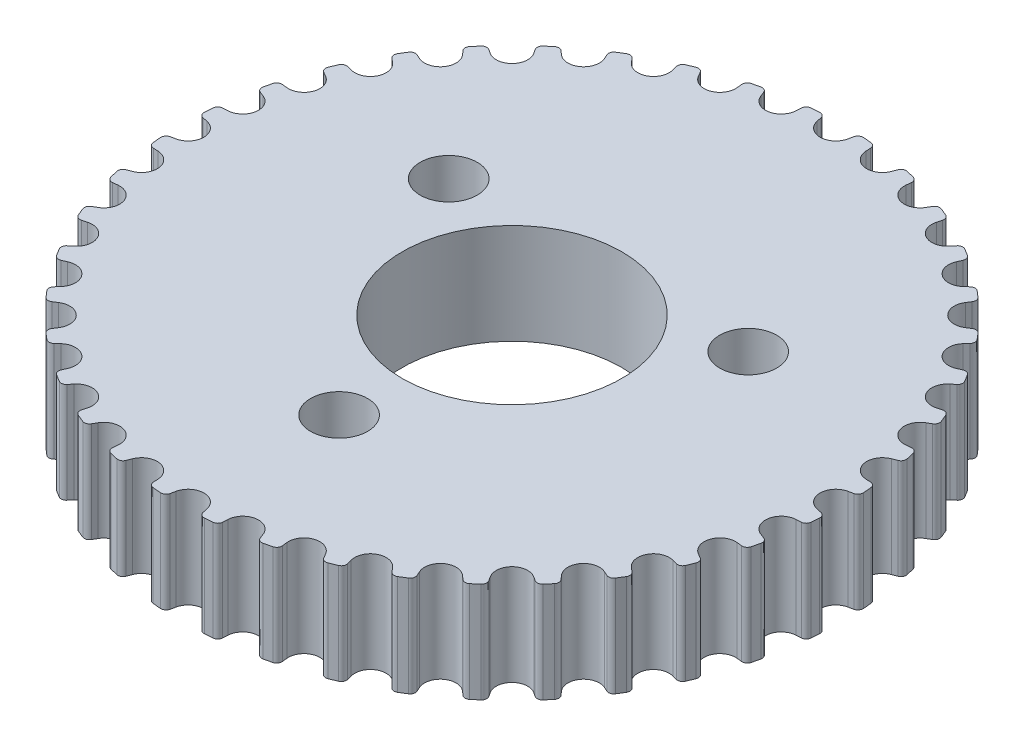
SolidWorks part; units mm, degrees
ref_plane "Front Plane" through (0, 0, 0) normal (0, 0, 1) x (1, 0, 0)
ref_plane "Top Plane" through (0, 0, 0) normal (0, 1, 0) x (1, 0, 0)
ref_plane "Right Plane" through (0, 0, 0) normal (1, 0, 0) x (0, 0, -1)
sketch "Sketch1" plane through (0, 0, 0) normal (0, 1, 0) x (1, 0, 0)
  circle A0 centre (0, 0) radius 19.0986
  dimension "D1" = 38.1972
extrude "Boss-Extrude1" add sketch "Sketch1" along normal blind 5.8
sketch "Sketch2" plane through (0, 5.8, 0) normal (0, 1, 0) x (1, 0, 0)
  line L0 (0, 0) -> (0, 19.0986) construction
  line L1 (-0.89, 18.5387) -> (-0.95, 18.82)
  line L2 (-2.9877, 18.8635) -> (-2.9877, 19.0986)
  line L3 (-2.9877, 19.0986) -> (2.9877, 19.0986)
  line L4 (0.89, 18.5387) -> (0.95, 18.82)
  line L5 (2.9877, 18.8635) -> (2.9877, 19.0986)
  circle A0 centre (0, 0) radius 19.0986 construction
  arc A1 (0.89, 18.5387) -> (-0.89, 18.5387) centre (0, 18.7286) cw
  arc A2 (-0.95, 18.82) -> (-1.2632, 19.0568) centre (-1.2434, 18.7574) ccw
  arc A4 (0.95, 18.82) -> (1.2632, 19.0568) centre (1.2434, 18.7574) cw
  arc A5 (-1.2632, 19.0568) -> (-2.9877, 18.8635) centre (0, 0) ccw
  arc A6 (1.2632, 19.0568) -> (2.9877, 18.8635) centre (0, 0) cw
  circle A8 centre (0, 0) radius 19.0986 construction
  point P11 (0, 19.0986)
  point P19 (0, 17.8186)
  dimension "D3" = 0.3
  dimension "D5" = 0.91
  dimension "D2" = 0.95
  dimension "D4" = 1.28
  dimension "D6" = 9
extrude "Cut-Extrude1" cut sketch "Sketch2" against normal through all
pattern_circular "CirPattern1" count 40 over 360 about axis through (0, 5.8, 0) along (0, -1, 0) of "Cut-Extrude1"
sketch "Sketch3" plane through (0, 0, 0) normal (0, -1, 0) x (1, 0, 0)
  circle A0 centre (0, 0) radius 6.35
  dimension "D1" = 12.7
extrude "Cut-Extrude2" cut sketch "Sketch3" against normal through all
sketch "Sketch4" plane through (0, 0, 0) normal (0, -1, 0) x (1, 0, 0)
  line L0 (0, 0) -> (0, 10) construction
  circle A0 centre (0, 10) radius 1.65
  circle A1 centre (8.6603, -5) radius 1.65
  circle A2 centre (-8.6603, -5) radius 1.65
  point P14 (0, 0)
  dimension "D1" = 3.3
  dimension "D2" = 10
  dimension "D3" = 3
extrude "Cut-Extrude3" cut sketch "Sketch4" against normal through all
sketch "Sketch5" plane through (0, 0, 0) normal (0, -1, 0) x (1, 0, 0)
  line L90 (-18.8409, 0.8522) -> (-18.5596, 0.7922)
  line L91 (-18.8409, 0.8522) -> (-18.5596, 0.7922)
  line L92 (-18.5596, -0.7922) -> (-18.8409, -0.8522)
  line L93 (-18.5596, -0.7922) -> (-18.8409, -0.8522)
  line L94 (-18.7423, -2.1057) -> (-18.455, -2.1209)
  line L95 (-18.7423, -2.1057) -> (-18.455, -2.1209)
  line L96 (-18.2071, -3.6858) -> (-18.4756, -3.7891)
  line L97 (-18.2071, -3.6858) -> (-18.4756, -3.7891)
  line L98 (-18.1821, -5.0117) -> (-17.896, -4.9818)
  line L99 (-18.1821, -5.0117) -> (-17.896, -4.9818)
  line L100 (-17.4064, -6.4886) -> (-17.6554, -6.6327)
  line L101 (-17.4064, -6.4886) -> (-17.6554, -6.6327)
  line L102 (-17.1743, -7.7943) -> (-16.8963, -7.72)
  line L103 (-17.1743, -7.7943) -> (-16.8963, -7.72)
  line L104 (-16.177, -9.1317) -> (-16.4005, -9.3129)
  line L105 (-16.177, -9.1317) -> (-16.4005, -9.3129)
  line L106 (-15.7435, -10.385) -> (-15.4806, -10.2682)
  line L107 (-15.7435, -10.385) -> (-15.4806, -10.2682)
  line L108 (-14.5494, -11.5499) -> (-14.7417, -11.7639)
  line L109 (-14.5494, -11.5499) -> (-14.7417, -11.7639)
  line L110 (-13.9251, -12.7199) -> (-13.6837, -12.5634)
  line L111 (-13.9251, -12.7199) -> (-13.6837, -12.5634)
  line L112 (-12.5634, -13.6837) -> (-12.7199, -13.9251)
  line L113 (-12.5634, -13.6837) -> (-12.7199, -13.9251)
  line L114 (-11.7639, -14.7417) -> (-11.5499, -14.5494)
  line L115 (-11.7639, -14.7417) -> (-11.5499, -14.5494)
  line L116 (-10.2682, -15.4806) -> (-10.385, -15.7435)
  line L117 (-10.2682, -15.4806) -> (-10.385, -15.7435)
  line L118 (-9.3129, -16.4005) -> (-9.1317, -16.177)
  line L119 (-9.3129, -16.4005) -> (-9.1317, -16.177)
  line L120 (6.4886, -17.4064) -> (6.6327, -17.6554)
  line L121 (7.7943, -17.1743) -> (7.72, -16.8963)
  line L122 (9.1317, -16.177) -> (9.3129, -16.4005)
  line L123 (10.385, -15.7435) -> (10.2682, -15.4806)
  line L124 (11.5499, -14.5494) -> (11.7639, -14.7417)
  line L125 (12.7199, -13.9251) -> (12.5634, -13.6837)
  line L126 (13.6837, -12.5634) -> (13.9251, -12.7199)
  line L127 (14.7417, -11.7639) -> (14.5494, -11.5499)
  line L128 (15.4806, -10.2682) -> (15.7435, -10.385)
  line L129 (16.4005, -9.3129) -> (16.177, -9.1317)
  line L130 (16.8963, -7.72) -> (17.1743, -7.7943)
  line L131 (17.6554, -6.6327) -> (17.4064, -6.4886)
  line L132 (17.896, -4.9818) -> (18.1821, -5.0117)
  line L133 (18.4756, -3.7891) -> (18.2071, -3.6858)
  line L134 (18.455, -2.1209) -> (18.7423, -2.1057)
  line L135 (18.8409, -0.8522) -> (18.5596, -0.7922)
  line L136 (18.5596, 0.7922) -> (18.8409, 0.8522)
  line L137 (18.7423, 2.1057) -> (18.455, 2.1209)
  line L138 (18.2071, 3.6858) -> (18.4756, 3.7891)
  line L139 (18.1821, 5.0117) -> (17.896, 4.9818)
  line L140 (17.4064, 6.4886) -> (17.6554, 6.6327)
  line L141 (17.1743, 7.7943) -> (16.8963, 7.72)
  line L142 (16.177, 9.1317) -> (16.4005, 9.3129)
  line L143 (15.7435, 10.385) -> (15.4806, 10.2682)
  line L144 (14.5494, 11.5499) -> (14.7417, 11.7639)
  line L145 (13.9251, 12.7199) -> (13.6837, 12.5634)
  line L146 (12.5634, 13.6837) -> (12.7199, 13.9251)
  line L147 (11.7639, 14.7417) -> (11.5499, 14.5494)
  line L148 (10.2682, 15.4806) -> (10.385, 15.7435)
  line L149 (9.3129, 16.4005) -> (9.1317, 16.177)
  line L150 (7.72, 16.8963) -> (7.7943, 17.1743)
  line L151 (6.6327, 17.6554) -> (6.4886, 17.4064)
  line L152 (4.9818, 17.896) -> (5.0117, 18.1821)
  line L153 (3.7891, 18.4756) -> (3.6858, 18.2071)
  line L154 (2.1209, 18.455) -> (2.1057, 18.7423)
  line L155 (0.8522, 18.8409) -> (0.7922, 18.5596)
  line L156 (-0.7922, 18.5596) -> (-0.8522, 18.8409)
  line L157 (-2.1057, 18.7423) -> (-2.1209, 18.455)
  line L158 (-3.6858, 18.2071) -> (-3.7891, 18.4756)
  line L159 (-5.0117, 18.1821) -> (-4.9818, 17.896)
  line L160 (-6.4886, 17.4064) -> (-6.6327, 17.6554)
  line L161 (-7.7943, 17.1743) -> (-7.72, 16.8963)
  line L162 (-9.1317, 16.177) -> (-9.3129, 16.4005)
  line L163 (-10.385, 15.7435) -> (-10.2682, 15.4806)
  line L164 (-11.5499, 14.5494) -> (-11.7639, 14.7417)
  line L165 (-12.7199, 13.9251) -> (-12.5634, 13.6837)
  line L166 (-13.6837, 12.5634) -> (-13.9251, 12.7199)
  line L167 (-14.7417, 11.7639) -> (-14.5494, 11.5499)
  line L168 (-15.4806, 10.2682) -> (-15.7435, 10.385)
  line L169 (-16.4005, 9.3129) -> (-16.177, 9.1317)
  line L170 (-16.8963, 7.72) -> (-17.1743, 7.7943)
  line L171 (-17.6554, 6.6327) -> (-17.4064, 6.4886)
  line L172 (-17.896, 4.9818) -> (-18.1821, 5.0117)
  line L173 (-18.4756, 3.7891) -> (-18.2071, 3.6858)
  line L174 (-18.455, 2.1209) -> (-18.7423, 2.1057)
  line L175 (-0.8522, -18.8409) -> (-0.7922, -18.5596)
  line L176 (0.7922, -18.5596) -> (0.8522, -18.8409)
  line L177 (2.1057, -18.7423) -> (2.1209, -18.455)
  line L178 (3.6858, -18.2071) -> (3.7891, -18.4756)
  line L179 (5.0117, -18.1821) -> (4.9818, -17.896)
  line L180 (6.4886, -17.4064) -> (6.6327, -17.6554)
  line L181 (7.7943, -17.1743) -> (7.72, -16.8963)
  line L182 (9.1317, -16.177) -> (9.3129, -16.4005)
  line L183 (10.385, -15.7435) -> (10.2682, -15.4806)
  line L184 (11.5499, -14.5494) -> (11.7639, -14.7417)
  line L185 (12.7199, -13.9251) -> (12.5634, -13.6837)
  line L186 (13.6837, -12.5634) -> (13.9251, -12.7199)
  line L187 (14.7417, -11.7639) -> (14.5494, -11.5499)
  line L188 (15.4806, -10.2682) -> (15.7435, -10.385)
  line L189 (16.4005, -9.3129) -> (16.177, -9.1317)
  line L190 (16.8963, -7.72) -> (17.1743, -7.7943)
  line L191 (17.6554, -6.6327) -> (17.4064, -6.4886)
  line L192 (17.896, -4.9818) -> (18.1821, -5.0117)
  line L193 (18.4756, -3.7891) -> (18.2071, -3.6858)
  line L194 (18.455, -2.1209) -> (18.7423, -2.1057)
  line L195 (18.8409, -0.8522) -> (18.5596, -0.7922)
  line L196 (18.5596, 0.7922) -> (18.8409, 0.8522)
  line L197 (18.7423, 2.1057) -> (18.455, 2.1209)
  line L198 (18.2071, 3.6858) -> (18.4756, 3.7891)
  line L199 (18.1821, 5.0117) -> (17.896, 4.9818)
  line L200 (17.4064, 6.4886) -> (17.6554, 6.6327)
  line L201 (17.1743, 7.7943) -> (16.8963, 7.72)
  line L202 (16.177, 9.1317) -> (16.4005, 9.3129)
  line L203 (15.7435, 10.385) -> (15.4806, 10.2682)
  line L204 (14.5494, 11.5499) -> (14.7417, 11.7639)
  line L205 (13.9251, 12.7199) -> (13.6837, 12.5634)
  line L206 (12.5634, 13.6837) -> (12.7199, 13.9251)
  line L207 (11.7639, 14.7417) -> (11.5499, 14.5494)
  line L208 (10.2682, 15.4806) -> (10.385, 15.7435)
  line L209 (9.3129, 16.4005) -> (9.1317, 16.177)
  line L210 (7.72, 16.8963) -> (7.7943, 17.1743)
  line L211 (6.6327, 17.6554) -> (6.4886, 17.4064)
  line L212 (4.9818, 17.896) -> (5.0117, 18.1821)
  line L213 (3.7891, 18.4756) -> (3.6858, 18.2071)
  line L214 (2.1209, 18.455) -> (2.1057, 18.7423)
  line L215 (0.8522, 18.8409) -> (0.7922, 18.5596)
  line L216 (-0.7922, 18.5596) -> (-0.8522, 18.8409)
  line L217 (-2.1057, 18.7423) -> (-2.1209, 18.455)
  line L218 (-3.6858, 18.2071) -> (-3.7891, 18.4756)
  line L219 (-5.0117, 18.1821) -> (-4.9818, 17.896)
  line L220 (-6.4886, 17.4064) -> (-6.6327, 17.6554)
  line L221 (-7.7943, 17.1743) -> (-7.72, 16.8963)
  line L222 (-9.1317, 16.177) -> (-9.3129, 16.4005)
  line L223 (-10.385, 15.7435) -> (-10.2682, 15.4806)
  line L224 (-11.5499, 14.5494) -> (-11.7639, 14.7417)
  line L225 (-12.7199, 13.9251) -> (-12.5634, 13.6837)
  line L226 (-13.6837, 12.5634) -> (-13.9251, 12.7199)
  line L227 (-14.7417, 11.7639) -> (-14.5494, 11.5499)
  line L228 (-15.4806, 10.2682) -> (-15.7435, 10.385)
  line L229 (-16.4005, 9.3129) -> (-16.177, 9.1317)
  line L230 (-16.8963, 7.72) -> (-17.1743, 7.7943)
  line L231 (-17.6554, 6.6327) -> (-17.4064, 6.4886)
  line L232 (-17.896, 4.9818) -> (-18.1821, 5.0117)
  line L233 (-18.4756, 3.7891) -> (-18.2071, 3.6858)
  line L234 (-18.455, 2.1209) -> (-18.7423, 2.1057)
  line L235 (-0.8522, -18.8409) -> (-0.7922, -18.5596)
  line L236 (0.7922, -18.5596) -> (0.8522, -18.8409)
  line L237 (2.1057, -18.7423) -> (2.1209, -18.455)
  line L238 (3.6858, -18.2071) -> (3.7891, -18.4756)
  line L239 (5.0117, -18.1821) -> (4.9818, -17.896)
  line L240 (-7.72, -16.8963) -> (-7.7943, -17.1743)
  line L241 (-7.72, -16.8963) -> (-7.7943, -17.1743)
  line L242 (-6.6327, -17.6554) -> (-6.4886, -17.4064)
  line L243 (-6.6327, -17.6554) -> (-6.4886, -17.4064)
  line L244 (-4.9818, -17.896) -> (-5.0117, -18.1821)
  line L245 (-4.9818, -17.896) -> (-5.0117, -18.1821)
  line L246 (-3.7891, -18.4756) -> (-3.6858, -18.2071)
  line L247 (-3.7891, -18.4756) -> (-3.6858, -18.2071)
  line L248 (-2.1209, -18.455) -> (-2.1057, -18.7423)
  line L249 (-2.1209, -18.455) -> (-2.1057, -18.7423)
  circle A120 centre (0, 0) radius 17.8186
  arc A121 (12.4795, 13.7381) -> (13.7381, 12.4795) centre (13.2431, 13.2431) ccw construction
  arc A182 (-19.1566, 1.2699) -> (-18.8409, 0.8522) centre (-18.7574, 1.2434) ccw
  arc A183 (-19.1566, 1.2699) -> (-18.8409, 0.8522) centre (-18.7574, 1.2434) ccw
  arc A184 (-18.5596, -0.7922) -> (-18.5596, 0.7922) centre (-18.7286, 0) ccw
  arc A185 (-18.5596, -0.7922) -> (-18.5596, 0.7922) centre (-18.7286, 0) ccw
  arc A186 (-18.8409, -0.8522) -> (-19.1566, -1.2699) centre (-18.7574, -1.2434) ccw
  arc A187 (-18.8409, -0.8522) -> (-19.1566, -1.2699) centre (-18.7574, -1.2434) ccw
  arc A188 (-19.1566, -1.2699) -> (-19.1194, -1.7425) centre (0, 0) ccw
  arc A189 (-19.1566, -1.2699) -> (-19.1194, -1.7425) centre (0, 0) ccw
  arc A190 (-19.1194, -1.7425) -> (-18.7423, -2.1057) centre (-18.721, -1.7062) ccw
  arc A191 (-19.1194, -1.7425) -> (-18.7423, -2.1057) centre (-18.721, -1.7062) ccw
  arc A192 (-18.2071, -3.6858) -> (-18.455, -2.1209) centre (-18.498, -2.9298) ccw
  arc A193 (-18.2071, -3.6858) -> (-18.455, -2.1209) centre (-18.498, -2.9298) ccw
  arc A194 (-18.4756, -3.7891) -> (-18.7221, -4.251) centre (-18.332, -4.1624) ccw
  arc A195 (-18.4756, -3.7891) -> (-18.7221, -4.251) centre (-18.332, -4.1624) ccw
  arc A196 (-18.7221, -4.251) -> (-18.6114, -4.712) centre (0, 0) ccw
  arc A197 (-18.7221, -4.251) -> (-18.6114, -4.712) centre (0, 0) ccw
  arc A198 (-18.6114, -4.712) -> (-18.1821, -5.0117) centre (-18.2236, -4.6138) ccw
  arc A199 (-18.6114, -4.712) -> (-18.1821, -5.0117) centre (-18.2236, -4.6138) ccw
  arc A200 (-17.4064, -6.4886) -> (-17.896, -4.9818) centre (-17.812, -5.7875) ccw
  arc A201 (-17.4064, -6.4886) -> (-17.896, -4.9818) centre (-17.812, -5.7875) ccw
  arc A202 (-17.6554, -6.6327) -> (-17.8266, -7.1274) centre (-17.4551, -6.9789) ccw
  arc A203 (-17.6554, -6.6327) -> (-17.8266, -7.1274) centre (-17.4551, -6.9789) ccw
  arc A204 (-17.8266, -7.1274) -> (-17.6451, -7.5654) centre (0, 0) ccw
  arc A205 (-17.8266, -7.1274) -> (-17.6451, -7.5654) centre (0, 0) ccw
  arc A206 (-17.6451, -7.5654) -> (-17.1743, -7.7943) centre (-17.2775, -7.4078) ccw
  arc A207 (-17.6451, -7.5654) -> (-17.1743, -7.7943) centre (-17.2775, -7.4078) ccw
  arc A208 (-16.177, -9.1317) -> (-16.8963, -7.72) centre (-16.6873, -8.5026) ccw
  arc A209 (-16.177, -9.1317) -> (-16.8963, -7.72) centre (-16.6873, -8.5026) ccw
  arc A210 (-16.4005, -9.3129) -> (-16.4921, -9.8283) centre (-16.1485, -9.6236) ccw
  arc A211 (-16.4005, -9.3129) -> (-16.4921, -9.8283) centre (-16.1485, -9.6236) ccw
  arc A212 (-16.4921, -9.8283) -> (-16.2444, -10.2326) centre (0, 0) ccw
  arc A213 (-16.4921, -9.8283) -> (-16.2444, -10.2326) centre (0, 0) ccw
  arc A214 (-16.2444, -10.2326) -> (-15.7435, -10.385) centre (-15.9059, -10.0194) ccw
  arc A215 (-16.2444, -10.2326) -> (-15.7435, -10.385) centre (-15.9059, -10.0194) ccw
  arc A216 (-14.5494, -11.5499) -> (-15.4806, -10.2682) centre (-15.1518, -11.0084) ccw
  arc A217 (-14.5494, -11.5499) -> (-15.4806, -10.2682) centre (-15.1518, -11.0084) ccw
  arc A218 (-14.7417, -11.7639) -> (-14.7516, -12.2873) centre (-14.4442, -12.0313) ccw
  arc A219 (-14.7417, -11.7639) -> (-14.7516, -12.2873) centre (-14.4442, -12.0313) ccw
  arc A220 (-14.7516, -12.2873) -> (-14.4436, -12.6478) centre (0, 0) ccw
  arc A221 (-14.7516, -12.2873) -> (-14.4436, -12.6478) centre (0, 0) ccw
  arc A222 (-14.4436, -12.6478) -> (-13.9251, -12.7199) centre (-14.1427, -12.3843) ccw
  arc A223 (-14.4436, -12.6478) -> (-13.9251, -12.7199) centre (-14.1427, -12.3843) ccw
  arc A224 (-12.5634, -13.6837) -> (-13.6837, -12.5634) centre (-13.2431, -13.2431) ccw
  arc A225 (-12.5634, -13.6837) -> (-13.6837, -12.5634) centre (-13.2431, -13.2431) ccw
  arc A226 (-12.7199, -13.9251) -> (-12.6478, -14.4436) centre (-12.3843, -14.1427) ccw
  arc A227 (-12.7199, -13.9251) -> (-12.6478, -14.4436) centre (-12.3843, -14.1427) ccw
  arc A228 (-12.6478, -14.4436) -> (-12.2873, -14.7516) centre (0, 0) ccw
  arc A229 (-12.6478, -14.4436) -> (-12.2873, -14.7516) centre (0, 0) ccw
  arc A230 (-12.2873, -14.7516) -> (-11.7639, -14.7417) centre (-12.0313, -14.4442) ccw
  arc A231 (-12.2873, -14.7516) -> (-11.7639, -14.7417) centre (-12.0313, -14.4442) ccw
  arc A232 (-10.2682, -15.4806) -> (-11.5499, -14.5494) centre (-11.0084, -15.1518) ccw
  arc A233 (-10.2682, -15.4806) -> (-11.5499, -14.5494) centre (-11.0084, -15.1518) ccw
  arc A234 (-10.385, -15.7435) -> (-10.2326, -16.2444) centre (-10.0194, -15.9059) ccw
  arc A235 (-10.385, -15.7435) -> (-10.2326, -16.2444) centre (-10.0194, -15.9059) ccw
  arc A236 (-10.2326, -16.2444) -> (-9.8283, -16.4921) centre (0, 0) ccw
  arc A237 (-10.2326, -16.2444) -> (-9.8283, -16.4921) centre (0, 0) ccw
  arc A238 (-9.8283, -16.4921) -> (-9.3129, -16.4005) centre (-9.6236, -16.1485) ccw
  arc A239 (-9.8283, -16.4921) -> (-9.3129, -16.4005) centre (-9.6236, -16.1485) ccw
  arc A240 (6.6327, -17.6554) -> (7.1274, -17.8266) centre (6.9789, -17.4551) ccw
  arc A241 (7.1274, -17.8266) -> (7.5654, -17.6451) centre (0, 0) ccw
  arc A242 (7.5654, -17.6451) -> (7.7943, -17.1743) centre (7.4078, -17.2775) ccw
  arc A243 (9.1317, -16.177) -> (7.72, -16.8963) centre (8.5026, -16.6873) ccw
  arc A244 (9.3129, -16.4005) -> (9.8283, -16.4921) centre (9.6236, -16.1485) ccw
  arc A245 (9.8283, -16.4921) -> (10.2326, -16.2444) centre (0, 0) ccw
  arc A246 (10.2326, -16.2444) -> (10.385, -15.7435) centre (10.0194, -15.9059) ccw
  arc A247 (11.5499, -14.5494) -> (10.2682, -15.4806) centre (11.0084, -15.1518) ccw
  arc A248 (11.7639, -14.7417) -> (12.2873, -14.7516) centre (12.0313, -14.4442) ccw
  arc A249 (12.2873, -14.7516) -> (12.6478, -14.4436) centre (0, 0) ccw
  arc A250 (12.6478, -14.4436) -> (12.7199, -13.9251) centre (12.3843, -14.1427) ccw
  arc A251 (13.6837, -12.5634) -> (12.5634, -13.6837) centre (13.2431, -13.2431) ccw
  arc A252 (13.9251, -12.7199) -> (14.4436, -12.6478) centre (14.1427, -12.3843) ccw
  arc A253 (14.4436, -12.6478) -> (14.7516, -12.2873) centre (0, 0) ccw
  arc A254 (14.7516, -12.2873) -> (14.7417, -11.7639) centre (14.4442, -12.0313) ccw
  arc A255 (15.4806, -10.2682) -> (14.5494, -11.5499) centre (15.1518, -11.0084) ccw
  arc A256 (15.7435, -10.385) -> (16.2444, -10.2326) centre (15.9059, -10.0194) ccw
  arc A257 (16.2444, -10.2326) -> (16.4921, -9.8283) centre (0, 0) ccw
  arc A258 (16.4921, -9.8283) -> (16.4005, -9.3129) centre (16.1485, -9.6236) ccw
  arc A259 (16.8963, -7.72) -> (16.177, -9.1317) centre (16.6873, -8.5026) ccw
  arc A260 (17.1743, -7.7943) -> (17.6451, -7.5654) centre (17.2775, -7.4078) ccw
  arc A261 (17.6451, -7.5654) -> (17.8266, -7.1274) centre (0, 0) ccw
  arc A262 (17.8266, -7.1274) -> (17.6554, -6.6327) centre (17.4551, -6.9789) ccw
  arc A263 (17.896, -4.9818) -> (17.4064, -6.4886) centre (17.812, -5.7875) ccw
  arc A264 (18.1821, -5.0117) -> (18.6114, -4.712) centre (18.2236, -4.6138) ccw
  arc A265 (18.6114, -4.712) -> (18.7221, -4.251) centre (0, 0) ccw
  arc A266 (18.7221, -4.251) -> (18.4756, -3.7891) centre (18.332, -4.1624) ccw
  arc A267 (18.455, -2.1209) -> (18.2071, -3.6858) centre (18.498, -2.9298) ccw
  arc A268 (18.7423, -2.1057) -> (19.1194, -1.7425) centre (18.721, -1.7062) ccw
  arc A269 (19.1194, -1.7425) -> (19.1566, -1.2699) centre (0, 0) ccw
  arc A270 (19.1566, -1.2699) -> (18.8409, -0.8522) centre (18.7574, -1.2434) ccw
  arc A271 (18.5596, 0.7922) -> (18.5596, -0.7922) centre (18.7286, 0) ccw
  arc A272 (18.8409, 0.8522) -> (19.1566, 1.2699) centre (18.7574, 1.2434) ccw
  arc A273 (19.1566, 1.2699) -> (19.1194, 1.7425) centre (0, 0) ccw
  arc A274 (19.1194, 1.7425) -> (18.7423, 2.1057) centre (18.721, 1.7062) ccw
  arc A275 (18.2071, 3.6858) -> (18.455, 2.1209) centre (18.498, 2.9298) ccw
  arc A276 (18.4756, 3.7891) -> (18.7221, 4.251) centre (18.332, 4.1624) ccw
  arc A277 (18.7221, 4.251) -> (18.6114, 4.712) centre (0, 0) ccw
  arc A278 (18.6114, 4.712) -> (18.1821, 5.0117) centre (18.2236, 4.6138) ccw
  arc A279 (17.4064, 6.4886) -> (17.896, 4.9818) centre (17.812, 5.7875) ccw
  arc A280 (17.6554, 6.6327) -> (17.8266, 7.1274) centre (17.4551, 6.9789) ccw
  arc A281 (17.8266, 7.1274) -> (17.6451, 7.5654) centre (0, 0) ccw
  arc A282 (17.6451, 7.5654) -> (17.1743, 7.7943) centre (17.2775, 7.4078) ccw
  arc A283 (16.177, 9.1317) -> (16.8963, 7.72) centre (16.6873, 8.5026) ccw
  arc A284 (16.4005, 9.3129) -> (16.4921, 9.8283) centre (16.1485, 9.6236) ccw
  arc A285 (16.4921, 9.8283) -> (16.2444, 10.2326) centre (0, 0) ccw
  arc A286 (16.2444, 10.2326) -> (15.7435, 10.385) centre (15.9059, 10.0194) ccw
  arc A287 (14.5494, 11.5499) -> (15.4806, 10.2682) centre (15.1518, 11.0084) ccw
  arc A288 (14.7417, 11.7639) -> (14.7516, 12.2873) centre (14.4442, 12.0313) ccw
  arc A289 (14.7516, 12.2873) -> (14.4436, 12.6478) centre (0, 0) ccw
  arc A290 (14.4436, 12.6478) -> (13.9251, 12.7199) centre (14.1427, 12.3843) ccw
  arc A291 (12.5634, 13.6837) -> (13.6837, 12.5634) centre (13.2431, 13.2431) ccw
  arc A292 (12.7199, 13.9251) -> (12.6478, 14.4436) centre (12.3843, 14.1427) ccw
  arc A293 (12.6478, 14.4436) -> (12.2873, 14.7516) centre (0, 0) ccw
  arc A294 (12.2873, 14.7516) -> (11.7639, 14.7417) centre (12.0313, 14.4442) ccw
  arc A295 (10.2682, 15.4806) -> (11.5499, 14.5494) centre (11.0084, 15.1518) ccw
  arc A296 (10.385, 15.7435) -> (10.2326, 16.2444) centre (10.0194, 15.9059) ccw
  arc A297 (10.2326, 16.2444) -> (9.8283, 16.4921) centre (0, 0) ccw
  arc A298 (9.8283, 16.4921) -> (9.3129, 16.4005) centre (9.6236, 16.1485) ccw
  arc A299 (7.72, 16.8963) -> (9.1317, 16.177) centre (8.5026, 16.6873) ccw
  arc A300 (7.7943, 17.1743) -> (7.5654, 17.6451) centre (7.4078, 17.2775) ccw
  arc A301 (7.5654, 17.6451) -> (7.1274, 17.8266) centre (0, 0) ccw
  arc A302 (7.1274, 17.8266) -> (6.6327, 17.6554) centre (6.9789, 17.4551) ccw
  arc A303 (4.9818, 17.896) -> (6.4886, 17.4064) centre (5.7875, 17.812) ccw
  arc A304 (5.0117, 18.1821) -> (4.712, 18.6114) centre (4.6138, 18.2236) ccw
  arc A305 (4.712, 18.6114) -> (4.251, 18.7221) centre (0, 0) ccw
  arc A306 (4.251, 18.7221) -> (3.7891, 18.4756) centre (4.1624, 18.332) ccw
  arc A307 (2.1209, 18.455) -> (3.6858, 18.2071) centre (2.9298, 18.498) ccw
  arc A308 (2.1057, 18.7423) -> (1.7425, 19.1194) centre (1.7062, 18.721) ccw
  arc A309 (1.7425, 19.1194) -> (1.2699, 19.1566) centre (0, 0) ccw
  arc A310 (1.2699, 19.1566) -> (0.8522, 18.8409) centre (1.2434, 18.7574) ccw
  arc A311 (-0.7922, 18.5596) -> (0.7922, 18.5596) centre (0, 18.7286) ccw
  arc A312 (-0.8522, 18.8409) -> (-1.2699, 19.1566) centre (-1.2434, 18.7574) ccw
  arc A313 (-1.2699, 19.1566) -> (-1.7425, 19.1194) centre (0, 0) ccw
  arc A314 (-1.7425, 19.1194) -> (-2.1057, 18.7423) centre (-1.7062, 18.721) ccw
  arc A315 (-3.6858, 18.2071) -> (-2.1209, 18.455) centre (-2.9298, 18.498) ccw
  arc A316 (-3.7891, 18.4756) -> (-4.251, 18.7221) centre (-4.1624, 18.332) ccw
  arc A317 (-4.251, 18.7221) -> (-4.712, 18.6114) centre (0, 0) ccw
  arc A318 (-4.712, 18.6114) -> (-5.0117, 18.1821) centre (-4.6138, 18.2236) ccw
  arc A319 (-6.4886, 17.4064) -> (-4.9818, 17.896) centre (-5.7875, 17.812) ccw
  arc A320 (-6.6327, 17.6554) -> (-7.1274, 17.8266) centre (-6.9789, 17.4551) ccw
  arc A321 (-7.1274, 17.8266) -> (-7.5654, 17.6451) centre (0, 0) ccw
  arc A322 (-7.5654, 17.6451) -> (-7.7943, 17.1743) centre (-7.4078, 17.2775) ccw
  arc A323 (-9.1317, 16.177) -> (-7.72, 16.8963) centre (-8.5026, 16.6873) ccw
  arc A324 (-9.3129, 16.4005) -> (-9.8283, 16.4921) centre (-9.6236, 16.1485) ccw
  arc A325 (-9.8283, 16.4921) -> (-10.2326, 16.2444) centre (0, 0) ccw
  arc A326 (-10.2326, 16.2444) -> (-10.385, 15.7435) centre (-10.0194, 15.9059) ccw
  arc A327 (-11.5499, 14.5494) -> (-10.2682, 15.4806) centre (-11.0084, 15.1518) ccw
  arc A328 (-11.7639, 14.7417) -> (-12.2873, 14.7516) centre (-12.0313, 14.4442) ccw
  arc A329 (-12.2873, 14.7516) -> (-12.6478, 14.4436) centre (0, 0) ccw
  arc A330 (-12.6478, 14.4436) -> (-12.7199, 13.9251) centre (-12.3843, 14.1427) ccw
  arc A331 (-13.6837, 12.5634) -> (-12.5634, 13.6837) centre (-13.2431, 13.2431) ccw
  arc A332 (-13.9251, 12.7199) -> (-14.4436, 12.6478) centre (-14.1427, 12.3843) ccw
  arc A333 (-14.4436, 12.6478) -> (-14.7516, 12.2873) centre (0, 0) ccw
  arc A334 (-14.7516, 12.2873) -> (-14.7417, 11.7639) centre (-14.4442, 12.0313) ccw
  arc A335 (-15.4806, 10.2682) -> (-14.5494, 11.5499) centre (-15.1518, 11.0084) ccw
  arc A336 (-15.7435, 10.385) -> (-16.2444, 10.2326) centre (-15.9059, 10.0194) ccw
  arc A337 (-16.2444, 10.2326) -> (-16.4921, 9.8283) centre (0, 0) ccw
  arc A338 (-16.4921, 9.8283) -> (-16.4005, 9.3129) centre (-16.1485, 9.6236) ccw
  arc A339 (-16.8963, 7.72) -> (-16.177, 9.1317) centre (-16.6873, 8.5026) ccw
  arc A340 (-17.1743, 7.7943) -> (-17.6451, 7.5654) centre (-17.2775, 7.4078) ccw
  arc A341 (-17.6451, 7.5654) -> (-17.8266, 7.1274) centre (0, 0) ccw
  arc A342 (-17.8266, 7.1274) -> (-17.6554, 6.6327) centre (-17.4551, 6.9789) ccw
  arc A343 (-17.896, 4.9818) -> (-17.4064, 6.4886) centre (-17.812, 5.7875) ccw
  arc A344 (-18.1821, 5.0117) -> (-18.6114, 4.712) centre (-18.2236, 4.6138) ccw
  arc A345 (-18.6114, 4.712) -> (-18.7221, 4.251) centre (0, 0) ccw
  arc A346 (-18.7221, 4.251) -> (-18.4756, 3.7891) centre (-18.332, 4.1624) ccw
  arc A347 (-18.455, 2.1209) -> (-18.2071, 3.6858) centre (-18.498, 2.9298) ccw
  arc A348 (-18.7423, 2.1057) -> (-19.1194, 1.7425) centre (-18.721, 1.7062) ccw
  arc A349 (-19.1194, 1.7425) -> (-19.1566, 1.2699) centre (0, 0) ccw
  arc A350 (-1.2699, -19.1566) -> (-0.8522, -18.8409) centre (-1.2434, -18.7574) ccw
  arc A351 (0.7922, -18.5596) -> (-0.7922, -18.5596) centre (0, -18.7286) ccw
  arc A352 (0.8522, -18.8409) -> (1.2699, -19.1566) centre (1.2434, -18.7574) ccw
  arc A353 (1.2699, -19.1566) -> (1.7425, -19.1194) centre (0, 0) ccw
  arc A354 (1.7425, -19.1194) -> (2.1057, -18.7423) centre (1.7062, -18.721) ccw
  arc A355 (3.6858, -18.2071) -> (2.1209, -18.455) centre (2.9298, -18.498) ccw
  arc A356 (3.7891, -18.4756) -> (4.251, -18.7221) centre (4.1624, -18.332) ccw
  arc A357 (4.251, -18.7221) -> (4.712, -18.6114) centre (0, 0) ccw
  arc A358 (4.712, -18.6114) -> (5.0117, -18.1821) centre (4.6138, -18.2236) ccw
  arc A359 (6.4886, -17.4064) -> (4.9818, -17.896) centre (5.7875, -17.812) ccw
  arc A360 (6.6327, -17.6554) -> (7.1274, -17.8266) centre (6.9789, -17.4551) ccw
  arc A361 (7.1274, -17.8266) -> (7.5654, -17.6451) centre (0, 0) ccw
  arc A362 (7.5654, -17.6451) -> (7.7943, -17.1743) centre (7.4078, -17.2775) ccw
  arc A363 (9.1317, -16.177) -> (7.72, -16.8963) centre (8.5026, -16.6873) ccw
  arc A364 (9.3129, -16.4005) -> (9.8283, -16.4921) centre (9.6236, -16.1485) ccw
  arc A365 (9.8283, -16.4921) -> (10.2326, -16.2444) centre (0, 0) ccw
  arc A366 (10.2326, -16.2444) -> (10.385, -15.7435) centre (10.0194, -15.9059) ccw
  arc A367 (11.5499, -14.5494) -> (10.2682, -15.4806) centre (11.0084, -15.1518) ccw
  arc A368 (11.7639, -14.7417) -> (12.2873, -14.7516) centre (12.0313, -14.4442) ccw
  arc A369 (12.2873, -14.7516) -> (12.6478, -14.4436) centre (0, 0) ccw
  arc A370 (12.6478, -14.4436) -> (12.7199, -13.9251) centre (12.3843, -14.1427) ccw
  arc A371 (13.6837, -12.5634) -> (12.5634, -13.6837) centre (13.2431, -13.2431) ccw
  arc A372 (13.9251, -12.7199) -> (14.4436, -12.6478) centre (14.1427, -12.3843) ccw
  arc A373 (14.4436, -12.6478) -> (14.7516, -12.2873) centre (0, 0) ccw
  arc A374 (14.7516, -12.2873) -> (14.7417, -11.7639) centre (14.4442, -12.0313) ccw
  arc A375 (15.4806, -10.2682) -> (14.5494, -11.5499) centre (15.1518, -11.0084) ccw
  arc A376 (15.7435, -10.385) -> (16.2444, -10.2326) centre (15.9059, -10.0194) ccw
  arc A377 (16.2444, -10.2326) -> (16.4921, -9.8283) centre (0, 0) ccw
  arc A378 (16.4921, -9.8283) -> (16.4005, -9.3129) centre (16.1485, -9.6236) ccw
  arc A379 (16.8963, -7.72) -> (16.177, -9.1317) centre (16.6873, -8.5026) ccw
  arc A380 (17.1743, -7.7943) -> (17.6451, -7.5654) centre (17.2775, -7.4078) ccw
  arc A381 (17.6451, -7.5654) -> (17.8266, -7.1274) centre (0, 0) ccw
  arc A382 (17.8266, -7.1274) -> (17.6554, -6.6327) centre (17.4551, -6.9789) ccw
  arc A383 (17.896, -4.9818) -> (17.4064, -6.4886) centre (17.812, -5.7875) ccw
  arc A384 (18.1821, -5.0117) -> (18.6114, -4.712) centre (18.2236, -4.6138) ccw
  arc A385 (18.6114, -4.712) -> (18.7221, -4.251) centre (0, 0) ccw
  arc A386 (18.7221, -4.251) -> (18.4756, -3.7891) centre (18.332, -4.1624) ccw
  arc A387 (18.455, -2.1209) -> (18.2071, -3.6858) centre (18.498, -2.9298) ccw
  arc A388 (18.7423, -2.1057) -> (19.1194, -1.7425) centre (18.721, -1.7062) ccw
  arc A389 (19.1194, -1.7425) -> (19.1566, -1.2699) centre (0, 0) ccw
  arc A390 (19.1566, -1.2699) -> (18.8409, -0.8522) centre (18.7574, -1.2434) ccw
  arc A391 (18.5596, 0.7922) -> (18.5596, -0.7922) centre (18.7286, 0) ccw
  arc A392 (18.8409, 0.8522) -> (19.1566, 1.2699) centre (18.7574, 1.2434) ccw
  arc A393 (19.1566, 1.2699) -> (19.1194, 1.7425) centre (0, 0) ccw
  arc A394 (19.1194, 1.7425) -> (18.7423, 2.1057) centre (18.721, 1.7062) ccw
  arc A395 (18.2071, 3.6858) -> (18.455, 2.1209) centre (18.498, 2.9298) ccw
  arc A396 (18.4756, 3.7891) -> (18.7221, 4.251) centre (18.332, 4.1624) ccw
  arc A397 (18.7221, 4.251) -> (18.6114, 4.712) centre (0, 0) ccw
  arc A398 (18.6114, 4.712) -> (18.1821, 5.0117) centre (18.2236, 4.6138) ccw
  arc A399 (17.4064, 6.4886) -> (17.896, 4.9818) centre (17.812, 5.7875) ccw
  arc A400 (17.6554, 6.6327) -> (17.8266, 7.1274) centre (17.4551, 6.9789) ccw
  arc A401 (17.8266, 7.1274) -> (17.6451, 7.5654) centre (0, 0) ccw
  arc A402 (17.6451, 7.5654) -> (17.1743, 7.7943) centre (17.2775, 7.4078) ccw
  arc A403 (16.177, 9.1317) -> (16.8963, 7.72) centre (16.6873, 8.5026) ccw
  arc A404 (16.4005, 9.3129) -> (16.4921, 9.8283) centre (16.1485, 9.6236) ccw
  arc A405 (16.4921, 9.8283) -> (16.2444, 10.2326) centre (0, 0) ccw
  arc A406 (16.2444, 10.2326) -> (15.7435, 10.385) centre (15.9059, 10.0194) ccw
  arc A407 (14.5494, 11.5499) -> (15.4806, 10.2682) centre (15.1518, 11.0084) ccw
  arc A408 (14.7417, 11.7639) -> (14.7516, 12.2873) centre (14.4442, 12.0313) ccw
  arc A409 (14.7516, 12.2873) -> (14.4436, 12.6478) centre (0, 0) ccw
  arc A410 (14.4436, 12.6478) -> (13.9251, 12.7199) centre (14.1427, 12.3843) ccw
  arc A411 (12.5634, 13.6837) -> (13.6837, 12.5634) centre (13.2431, 13.2431) ccw
  arc A412 (12.7199, 13.9251) -> (12.6478, 14.4436) centre (12.3843, 14.1427) ccw
  arc A413 (12.6478, 14.4436) -> (12.2873, 14.7516) centre (0, 0) ccw
  arc A414 (12.2873, 14.7516) -> (11.7639, 14.7417) centre (12.0313, 14.4442) ccw
  arc A415 (10.2682, 15.4806) -> (11.5499, 14.5494) centre (11.0084, 15.1518) ccw
  arc A416 (10.385, 15.7435) -> (10.2326, 16.2444) centre (10.0194, 15.9059) ccw
  arc A417 (10.2326, 16.2444) -> (9.8283, 16.4921) centre (0, 0) ccw
  arc A418 (9.8283, 16.4921) -> (9.3129, 16.4005) centre (9.6236, 16.1485) ccw
  arc A419 (7.72, 16.8963) -> (9.1317, 16.177) centre (8.5026, 16.6873) ccw
  arc A420 (7.7943, 17.1743) -> (7.5654, 17.6451) centre (7.4078, 17.2775) ccw
  arc A421 (7.5654, 17.6451) -> (7.1274, 17.8266) centre (0, 0) ccw
  arc A422 (7.1274, 17.8266) -> (6.6327, 17.6554) centre (6.9789, 17.4551) ccw
  arc A423 (4.9818, 17.896) -> (6.4886, 17.4064) centre (5.7875, 17.812) ccw
  arc A424 (5.0117, 18.1821) -> (4.712, 18.6114) centre (4.6138, 18.2236) ccw
  arc A425 (4.712, 18.6114) -> (4.251, 18.7221) centre (0, 0) ccw
  arc A426 (4.251, 18.7221) -> (3.7891, 18.4756) centre (4.1624, 18.332) ccw
  arc A427 (2.1209, 18.455) -> (3.6858, 18.2071) centre (2.9298, 18.498) ccw
  arc A428 (2.1057, 18.7423) -> (1.7425, 19.1194) centre (1.7062, 18.721) ccw
  arc A429 (1.7425, 19.1194) -> (1.2699, 19.1566) centre (0, 0) ccw
  arc A430 (1.2699, 19.1566) -> (0.8522, 18.8409) centre (1.2434, 18.7574) ccw
  arc A431 (-0.7922, 18.5596) -> (0.7922, 18.5596) centre (0, 18.7286) ccw
  arc A432 (-0.8522, 18.8409) -> (-1.2699, 19.1566) centre (-1.2434, 18.7574) ccw
  arc A433 (-1.2699, 19.1566) -> (-1.7425, 19.1194) centre (0, 0) ccw
  arc A434 (-1.7425, 19.1194) -> (-2.1057, 18.7423) centre (-1.7062, 18.721) ccw
  arc A435 (-3.6858, 18.2071) -> (-2.1209, 18.455) centre (-2.9298, 18.498) ccw
  arc A436 (-3.7891, 18.4756) -> (-4.251, 18.7221) centre (-4.1624, 18.332) ccw
  arc A437 (-4.251, 18.7221) -> (-4.712, 18.6114) centre (0, 0) ccw
  arc A438 (-4.712, 18.6114) -> (-5.0117, 18.1821) centre (-4.6138, 18.2236) ccw
  arc A439 (-6.4886, 17.4064) -> (-4.9818, 17.896) centre (-5.7875, 17.812) ccw
  arc A440 (-6.6327, 17.6554) -> (-7.1274, 17.8266) centre (-6.9789, 17.4551) ccw
  arc A441 (-7.1274, 17.8266) -> (-7.5654, 17.6451) centre (0, 0) ccw
  arc A442 (-7.5654, 17.6451) -> (-7.7943, 17.1743) centre (-7.4078, 17.2775) ccw
  arc A443 (-9.1317, 16.177) -> (-7.72, 16.8963) centre (-8.5026, 16.6873) ccw
  arc A444 (-9.3129, 16.4005) -> (-9.8283, 16.4921) centre (-9.6236, 16.1485) ccw
  arc A445 (-9.8283, 16.4921) -> (-10.2326, 16.2444) centre (0, 0) ccw
  arc A446 (-10.2326, 16.2444) -> (-10.385, 15.7435) centre (-10.0194, 15.9059) ccw
  arc A447 (-11.5499, 14.5494) -> (-10.2682, 15.4806) centre (-11.0084, 15.1518) ccw
  arc A448 (-11.7639, 14.7417) -> (-12.2873, 14.7516) centre (-12.0313, 14.4442) ccw
  arc A449 (-12.2873, 14.7516) -> (-12.6478, 14.4436) centre (0, 0) ccw
  arc A450 (-12.6478, 14.4436) -> (-12.7199, 13.9251) centre (-12.3843, 14.1427) ccw
  arc A451 (-13.6837, 12.5634) -> (-12.5634, 13.6837) centre (-13.2431, 13.2431) ccw
  arc A452 (-13.9251, 12.7199) -> (-14.4436, 12.6478) centre (-14.1427, 12.3843) ccw
  arc A453 (-14.4436, 12.6478) -> (-14.7516, 12.2873) centre (0, 0) ccw
  arc A454 (-14.7516, 12.2873) -> (-14.7417, 11.7639) centre (-14.4442, 12.0313) ccw
  arc A455 (-15.4806, 10.2682) -> (-14.5494, 11.5499) centre (-15.1518, 11.0084) ccw
  arc A456 (-15.7435, 10.385) -> (-16.2444, 10.2326) centre (-15.9059, 10.0194) ccw
  arc A457 (-16.2444, 10.2326) -> (-16.4921, 9.8283) centre (0, 0) ccw
  arc A458 (-16.4921, 9.8283) -> (-16.4005, 9.3129) centre (-16.1485, 9.6236) ccw
  arc A459 (-16.8963, 7.72) -> (-16.177, 9.1317) centre (-16.6873, 8.5026) ccw
  arc A460 (-17.1743, 7.7943) -> (-17.6451, 7.5654) centre (-17.2775, 7.4078) ccw
  arc A461 (-17.6451, 7.5654) -> (-17.8266, 7.1274) centre (0, 0) ccw
  arc A462 (-17.8266, 7.1274) -> (-17.6554, 6.6327) centre (-17.4551, 6.9789) ccw
  arc A463 (-17.896, 4.9818) -> (-17.4064, 6.4886) centre (-17.812, 5.7875) ccw
  arc A464 (-18.1821, 5.0117) -> (-18.6114, 4.712) centre (-18.2236, 4.6138) ccw
  arc A465 (-18.6114, 4.712) -> (-18.7221, 4.251) centre (0, 0) ccw
  arc A466 (-18.7221, 4.251) -> (-18.4756, 3.7891) centre (-18.332, 4.1624) ccw
  arc A467 (-18.455, 2.1209) -> (-18.2071, 3.6858) centre (-18.498, 2.9298) ccw
  arc A468 (-18.7423, 2.1057) -> (-19.1194, 1.7425) centre (-18.721, 1.7062) ccw
  arc A469 (-19.1194, 1.7425) -> (-19.1566, 1.2699) centre (0, 0) ccw
  arc A470 (-1.2699, -19.1566) -> (-0.8522, -18.8409) centre (-1.2434, -18.7574) ccw
  arc A471 (0.7922, -18.5596) -> (-0.7922, -18.5596) centre (0, -18.7286) ccw
  arc A472 (0.8522, -18.8409) -> (1.2699, -19.1566) centre (1.2434, -18.7574) ccw
  arc A473 (1.2699, -19.1566) -> (1.7425, -19.1194) centre (0, 0) ccw
  arc A474 (1.7425, -19.1194) -> (2.1057, -18.7423) centre (1.7062, -18.721) ccw
  arc A475 (3.6858, -18.2071) -> (2.1209, -18.455) centre (2.9298, -18.498) ccw
  arc A476 (3.7891, -18.4756) -> (4.251, -18.7221) centre (4.1624, -18.332) ccw
  arc A477 (4.251, -18.7221) -> (4.712, -18.6114) centre (0, 0) ccw
  arc A478 (4.712, -18.6114) -> (5.0117, -18.1821) centre (4.6138, -18.2236) ccw
  arc A479 (6.4886, -17.4064) -> (4.9818, -17.896) centre (5.7875, -17.812) ccw
  arc A480 (-7.72, -16.8963) -> (-9.1317, -16.177) centre (-8.5026, -16.6873) ccw
  arc A481 (-7.72, -16.8963) -> (-9.1317, -16.177) centre (-8.5026, -16.6873) ccw
  arc A482 (-7.7943, -17.1743) -> (-7.5654, -17.6451) centre (-7.4078, -17.2775) ccw
  arc A483 (-7.7943, -17.1743) -> (-7.5654, -17.6451) centre (-7.4078, -17.2775) ccw
  arc A484 (-7.5654, -17.6451) -> (-7.1274, -17.8266) centre (0, 0) ccw
  arc A485 (-7.5654, -17.6451) -> (-7.1274, -17.8266) centre (0, 0) ccw
  arc A486 (-7.1274, -17.8266) -> (-6.6327, -17.6554) centre (-6.9789, -17.4551) ccw
  arc A487 (-7.1274, -17.8266) -> (-6.6327, -17.6554) centre (-6.9789, -17.4551) ccw
  arc A488 (-4.9818, -17.896) -> (-6.4886, -17.4064) centre (-5.7875, -17.812) ccw
  arc A489 (-4.9818, -17.896) -> (-6.4886, -17.4064) centre (-5.7875, -17.812) ccw
  arc A490 (-5.0117, -18.1821) -> (-4.712, -18.6114) centre (-4.6138, -18.2236) ccw
  arc A491 (-5.0117, -18.1821) -> (-4.712, -18.6114) centre (-4.6138, -18.2236) ccw
  arc A492 (-4.712, -18.6114) -> (-4.251, -18.7221) centre (0, 0) ccw
  arc A493 (-4.712, -18.6114) -> (-4.251, -18.7221) centre (0, 0) ccw
  arc A494 (-4.251, -18.7221) -> (-3.7891, -18.4756) centre (-4.1624, -18.332) ccw
  arc A495 (-4.251, -18.7221) -> (-3.7891, -18.4756) centre (-4.1624, -18.332) ccw
  arc A496 (-2.1209, -18.455) -> (-3.6858, -18.2071) centre (-2.9298, -18.498) ccw
  arc A497 (-2.1209, -18.455) -> (-3.6858, -18.2071) centre (-2.9298, -18.498) ccw
  arc A498 (-2.1057, -18.7423) -> (-1.7425, -19.1194) centre (-1.7062, -18.721) ccw
  arc A499 (-2.1057, -18.7423) -> (-1.7425, -19.1194) centre (-1.7062, -18.721) ccw
  arc A500 (-1.7425, -19.1194) -> (-1.2699, -19.1566) centre (0, 0) ccw
  arc A501 (-1.7425, -19.1194) -> (-1.2699, -19.1566) centre (0, 0) ccw
  dimension "D1" = 0.1
extrude "Boss-Extrude2" [suppressed] add sketch "Sketch5" against normal up to surface (5.8 mm away) up to face at (8.6603, 5.8, -6.65)
equation "\"smallPulleyTeeth\"= 15"
equation "\"largePulleyTeeth\"= 40"
equation "\"eighthThick\"= 2.9mm"
equation "\"D1@Sketch1\"=3*\"largePulleyTeeth\"/pi"
equation "\"D1@Boss-Extrude1\" = \"eighthThick\" * 2"
equation "\"D6@Sketch2\"=360/\"largePulleyTeeth\""
equation "\"quarterThick\"=5.9mm"
equation "\"D1@CirPattern1\"=\"largePulleyTeeth\""
equation "\"sixteenthThick\" = 1.7mm"
equation "\"OD\" = 145mm"
equation "\"puckAngle\" = 60.5deg"
equation "\"puckDiam\" = 76.5mm"
equation "\"axlePress\" = 5.9mm"
equation "\"press\" = 0.2mm"
equation "\"wheelClear\" = 0.3mm"
equation "\"10-32clear\" = 4.5mm"
equation "\"D1@Sketch4\"=\"6-32clear\""
equation "\"6-32clear\" = 3.3mm"
equation "\"8-32clear\" = 4.0mm"
